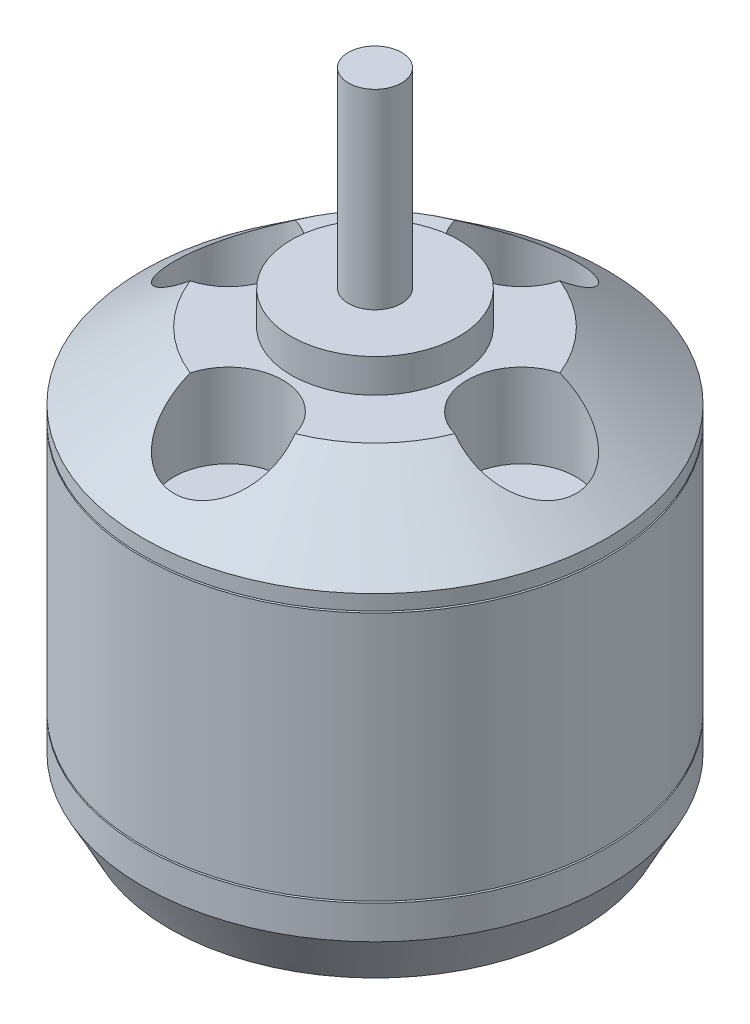
SolidWorks part; units mm, degrees
ref_plane "Front Plane" through (0, 0, 0) normal (0, 0, 1) x (1, 0, 0)
ref_plane "Top Plane" through (0, 0, 0) normal (0, 1, 0) x (1, 0, 0)
ref_plane "Right Plane" through (0, 0, 0) normal (1, 0, 0) x (0, 0, -1)
sketch "Sketch1" plane through (0, 0, 0) normal (0, 1, 0) x (1, 0, 0)
  circle A0 centre (0, 0) radius 13.85
  dimension "D1" = 27.7
extrude "Boss-Extrude1" add sketch "Sketch1" along normal blind 25
sketch "Sketch4" plane through (0, 0, 0) normal (1, 0, 0) x (0, 0, -1)
  line L0 (13.85, 3) -> (12.25, 0)
  line L1 (13.85, 0) -> (13.85, 25) construction
  line L2 (-13.85, 0) -> (13.85, 0) construction
  line L3 (12.25, 0) -> (13.85, 0)
  line L4 (13.85, 0) -> (13.85, 3)
  line L5 (0, 9.4624) -> (0, 4.4335) construction
  dimension "D1" = 12.25
  dimension "D2" = 3
revolve "Cut-Revolve1" cut sketch "Sketch4" angle 360 about L5
sketch "Sketch5" plane through (0, 0, 0) normal (1, 0, 0) x (0, 0, -1)
  line L0 (-8.5, 25) -> (-13.85, 21)
  line L1 (13.85, 25) -> (-13.85, 25) construction
  line L2 (-13.85, 25) -> (-13.85, 3) construction
  line L3 (-13.85, 21) -> (-13.85, 25)
  line L4 (-13.85, 25) -> (-8.5, 25)
  line L5 (0, 28.2012) -> (0, 18.7949) construction
  dimension "D1" = 8.5
  dimension "D2" = 4
revolve "Cut-Revolve2" cut sketch "Sketch5" angle 360 about L5
sketch "Sketch6" plane through (0, 0, 0) normal (0, -1, 0) x (1, 0, 0)
  circle A2 centre (0, 9.5) radius 1.5
  circle A3 centre (0, -9.5) radius 1.5
  circle A4 centre (8, 0) radius 1.5
  circle A5 centre (-8, 0) radius 1.5
  dimension "D3" = 3
  dimension "D4" = 3
  dimension "D5" = 3
  dimension "D6" = 3
extrude "Cut-Extrude1" cut sketch "Sketch6" against normal blind 4
sketch "Sketch7" plane through (0, 0, 0) normal (0, -1, 0) x (-1, 0, 0)
  circle A0 centre (0, 0) radius 5
  dimension "D1" = 10
extrude "Cut-Extrude2" cut sketch "Sketch7" against normal blind 1
chamfer "Chamfer1" distance 1 angle 45 1 edges at (0, 1, -5)
sketch "Sketch8" plane through (0, 25, 0) normal (0, 1, 0) x (1, 0, 0)
  circle A0 centre (0, 0) radius 5
  dimension "D1" = 10
extrude "Boss-Extrude2" add sketch "Sketch8" along normal blind 2
ref_plane "Plane2" through (0, 38.4, 0) normal (0, 1, 0) x (1, 0, 0)
sketch "Sketch9" plane through (0, 38.4, 0) normal (0, 1, 0) x (1, 0, 0)
  circle A0 centre (0, 0) radius 1.585
  dimension "D1" = 3.17
extrude "Boss-Extrude3" add sketch "Sketch9" against normal blind 40
sketch "Sketch10" plane through (0, 25, 0) normal (0, 1, 0) x (1, 0, 0)
  circle A0 centre (8.75, 0) radius 3.25
  circle A1 centre (0, -8.75) radius 3.25
  circle A2 centre (-8.75, 0) radius 3.25
  circle A3 centre (0, 8.75) radius 3.25
  point P12 (0, 0)
  dimension "D1" = 6.5
  dimension "D2" = 8.75
  dimension "D3" = 4
extrude "Cut-Extrude3" cut sketch "Sketch10" against normal blind 5
thread "Thread1" pitch 0.5 method cut profile "Thread Profile1" start angle 0, offset 0, length 0, pitch 0.5, diameter 3
ref_plane "Plane3" through (-6.5, 0, 0) normal (0, 0, 1) x (1, 0, 0)
sketch "Thread Profile1" plane through (-6.5, 0, 0) normal (0, 0, 1) x (1, 0, 0)
  line L0 (0, 0) -> (0, 0.5) construction
  line L1 (0, 0) -> (0.2706, 0.1562)
  line L2 (0.2706, 0.1562) -> (0.2706, 0.2187)
  line L3 (0.2706, 0.2187) -> (0, 0.375)
  line L4 (0.2706, 0.1875) -> (0, 0.1875) construction
  line L11 (0, 0) -> (0, 0.375)
  point P2 (0, 0)
  dimension "Pitch" = 0.5
  dimension "Profile_Angle" = 60
  dimension "Profile_Land" = 0.0625
  dimension "Profile_Height" = 0.2706
thread "Thread2" pitch 0.5 method cut profile "Thread Profile2" start angle 0, offset 0, length 0, pitch 0.5, diameter 3
ref_plane "Plane4" through (1.5, 0, 9.5) normal (0, 0, 1) x (1, 0, 0)
sketch "Thread Profile2" plane through (1.5, 0, 9.5) normal (0, 0, 1) x (1, 0, 0)
  line L0 (0, 0) -> (0, 0.5) construction
  line L1 (0, 0) -> (0.2706, 0.1562)
  line L2 (0.2706, 0.1562) -> (0.2706, 0.2187)
  line L3 (0.2706, 0.2187) -> (0, 0.375)
  line L4 (0.2706, 0.1875) -> (0, 0.1875) construction
  line L11 (0, 0) -> (0, 0.375)
  point P2 (0, 0)
  dimension "Pitch" = 0.5
  dimension "Profile_Angle" = 60
  dimension "Profile_Land" = 0.0625
  dimension "Profile_Height" = 0.2706
thread "Thread3" pitch 0.5 method cut profile "Thread Profile3" start angle 0, offset 0, length 0, pitch 0.5, diameter 3
ref_plane "Plane5" through (9.5, 0, 0) normal (0, 0, 1) x (1, 0, 0)
sketch "Thread Profile3" plane through (9.5, 0, 0) normal (0, 0, 1) x (1, 0, 0)
  line L0 (0, 0) -> (0, 0.5) construction
  line L1 (0, 0) -> (0.2706, 0.1562)
  line L2 (0.2706, 0.1562) -> (0.2706, 0.2187)
  line L3 (0.2706, 0.2187) -> (0, 0.375)
  line L4 (0.2706, 0.1875) -> (0, 0.1875) construction
  line L11 (0, 0) -> (0, 0.375)
  point P2 (0, 0)
  dimension "Pitch" = 0.5
  dimension "Profile_Angle" = 60
  dimension "Profile_Land" = 0.0625
  dimension "Profile_Height" = 0.2706
thread "Thread4" pitch 0.5 method cut profile "Thread Profile4" start angle 0, offset 0, length 0, pitch 0.5, diameter 3
ref_plane "Plane6" through (1.5, 0, -9.5) normal (0, 0, 1) x (1, 0, 0)
sketch "Thread Profile4" plane through (1.5, 0, -9.5) normal (0, 0, 1) x (1, 0, 0)
  line L0 (0, 0) -> (0, 0.5) construction
  line L1 (0, 0) -> (0.2706, 0.1562)
  line L2 (0.2706, 0.1562) -> (0.2706, 0.2187)
  line L3 (0.2706, 0.2187) -> (0, 0.375)
  line L4 (0.2706, 0.1875) -> (0, 0.1875) construction
  line L11 (0, 0) -> (0, 0.375)
  point P2 (0, 0)
  dimension "Pitch" = 0.5
  dimension "Profile_Angle" = 60
  dimension "Profile_Land" = 0.0625
  dimension "Profile_Height" = 0.2706
sketch "Sketch22" plane through (0, 0, 0) normal (1, 0, 0) x (0, 0, -1)
  line L0 (13.65, 5) -> (13.85, 5)
  line L1 (-13.85, 3) -> (13.85, 3) construction
  line L2 (13.85, 3) -> (13.85, 21) construction
  line L3 (13.65, 5) -> (13.65, 5.1)
  line L4 (13.65, 5.1) -> (13.85, 5.1)
  line L5 (13.85, 5.1) -> (13.85, 5)
  line L6 (13.85, 3) -> (13.85, 21) construction
  line L7 (13.85, 20) -> (13.65, 20)
  line L8 (13.85, 20) -> (13.85, 20.1)
  line L9 (13.85, 20.1) -> (13.65, 20.1)
  line L10 (13.65, 20) -> (13.65, 20.1)
  line L11 (-13.85, 21) -> (13.85, 21) construction
  line L12 (0, 15.5984) -> (0, 42.7675) construction
  dimension "D1" = 2
  dimension "D2" = 0.2
  dimension "D3" = 0.1
  dimension "D4" = 0.2
  dimension "D5" = 1
  dimension "D6" = 0.1
revolve "Cut-Revolve3" cut sketch "Sketch22" angle 360 about L12
